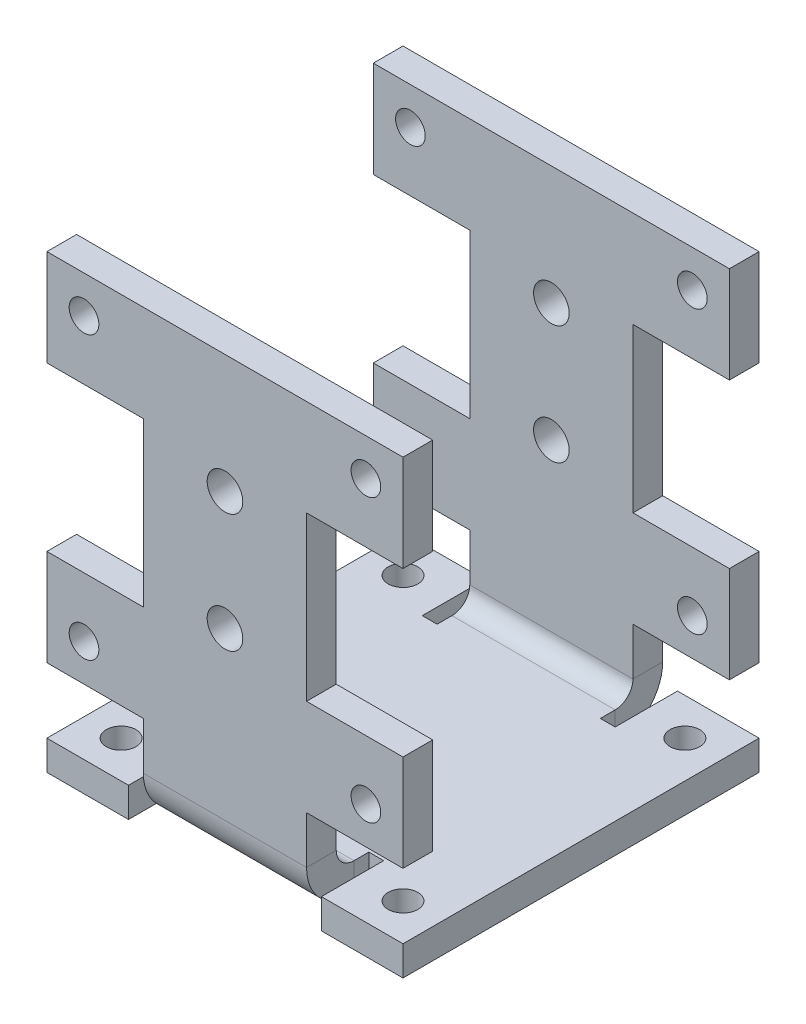
SolidWorks part; units mm, degrees
note: The reader was unsure of these and kept them because the rebuilt part matched: flange length of "边线-法兰1", "边线-法兰2".
material "5052-H36"
ref_plane "前视基准面" through (0, 0, 0) normal (0, 0, 1) x (1, 0, 0)
ref_plane "上视基准面" through (0, 0, 0) normal (0, 1, 0) x (1, 0, 0)
ref_plane "右视基准面" through (0, 0, 0) normal (1, 0, 0) x (0, 0, -1)
other "Configuration Table"
sketch "草图16" plane through (0, 0, 0) normal (0, 1, 0) x (1, 0, 0)
  line L0 (16.25, 30) -> (30, 30)
  line L5 (-30, -30) -> (-16.25, -30)
  line L6 (-30, -30) -> (-30, 30)
  line L11 (-30, 30) -> (-16.25, 30)
  line L12 (30, -30) -> (30, 30)
  line L17 (-30, -30) -> (30, 30) construction
  line L18 (-30, 30) -> (30, -30) construction
  line L19 (23.75, 23.75) -> (-23.75, 23.75) construction
  line L20 (23.75, 23.75) -> (23.75, -23.75) construction
  line L21 (23.75, -23.75) -> (-23.75, -23.75) construction
  line L22 (-23.75, 23.75) -> (-23.75, -23.75) construction
  line L23 (23.75, 23.75) -> (-23.75, -23.75) construction
  line L24 (23.75, -23.75) -> (-23.75, 23.75) construction
  line L26 (-16.25, 30) -> (-16.25, 23.75) construction
  line L27 (-16.25, 23.75) -> (16.25, 23.75) construction
  line L28 (16.25, 30) -> (16.25, 23.75) construction
  line L29 (-16.25, -23.75) -> (16.25, -23.75) construction
  line L30 (-16.25, -23.75) -> (-16.25, -30) construction
  line L32 (16.25, -23.75) -> (16.25, -30) construction
  line L33 (16.25, -30) -> (30, -30)
  line L34 (-16.25, -25) -> (-16.25, -30)
  line L35 (-16.25, -25) -> (16.25, -25)
  line L36 (-16.25, -25) -> (-16.25, 25) construction
  line L37 (-16.25, 25) -> (16.25, 25)
  line L38 (16.25, -25) -> (16.25, 25) construction
  line L39 (-16.25, -25) -> (16.25, 25) construction
  line L40 (-16.25, 25) -> (16.25, -25) construction
  line L41 (16.25, -25) -> (16.25, -30)
  line L42 (-16.25, 30) -> (-16.25, 25)
  line L43 (16.25, 30) -> (16.25, 25)
  circle A0 centre (-23.75, 23.75) radius 2.5
  circle A1 centre (-23.75, -23.75) radius 2.5
  circle A2 centre (-23.75, 23.75) radius 4.25 construction
  circle A3 centre (-23.75, -23.75) radius 4.25 construction
  circle A4 centre (23.75, 23.75) radius 2.5
  circle A5 centre (23.75, 23.75) radius 4.25 construction
  circle A6 centre (23.75, -23.75) radius 2.5
  circle A7 centre (23.75, -23.75) radius 4.25 construction
  point P0 (0, 0)
  point P6 (0, 0)
  point P23 (0, 0)
  point P24 (0, 23.75)
  point P29 (0, -23.75)
  dimension "D4" = 5
  dimension "D5" = 5
  dimension "D6" = 8.5
  dimension "D7" = 8.5
  dimension "D8" = 5
  dimension "D9" = 8.5
  dimension "D10" = 5
  dimension "D11" = 8.5
  dimension "D1" = 60
  dimension "D2" = 60
  dimension "D3" = 47.5
  dimension "D12" = 32.5
  dimension "D13" = 32.5
  dimension "D14" = 50
base flange "基体-法兰2" sketch "草图16" thickness 5 reverse thickness direction no parameters "D1"=0.7366
edge flange "边线-法兰1" sketch "草图19" flange angle 90 flange length 76 flange position material outside bend radius 3 thickness 5 relief rectangular parameters "D6"=10
sketch "草图19" plane through (0, 0, 25) normal (0, 0, 1) x (1, 0, 0)
  line L5 (-16.25, 0) -> (16.25, 0) construction
  line L6 (-13.75, 0) -> (13.75, 0)
  line L7 (-13.75, 0) -> (-13.75, 71)
  line L8 (-13.75, 71) -> (13.75, 71)
  line L9 (13.75, 0) -> (13.75, 71)
  point P6 (0, 0)
  dimension "D1" = 27.5
  dimension "D2" = 71
bend "边线折弯1" bend radius 3 bend angle 90 parameters "D5"=1
edge flange "边线-法兰2" sketch "草图22" flange angle 90 flange length 76 flange position material outside bend radius 3 thickness 5 relief rectangular parameters "D6"=10
sketch "草图22" plane through (0, 0, -25) normal (0, 0, -1) x (-1, 0, 0)
  line L6 (-13.75, 71) -> (13.75, 71)
  line L7 (-13.75, 71) -> (-13.75, 0)
  line L8 (-13.75, 0) -> (13.75, 0)
  line L9 (13.75, 71) -> (13.75, 0)
bend "边线折弯2" bend radius 3 bend angle 90 parameters "D5"=2
sketch "草图23" plane through (0, 0, 0) normal (0, 0, 1) x (1, 0, 0)
  line L0 (13.75, 71) -> (-13.75, 71) construction
  line L1 (-30, 71) -> (30, 71) construction
  line L2 (-30, 71) -> (-30, 11) construction
  line L3 (-30, 11) -> (30, 11) construction
  line L4 (30, 71) -> (30, 11) construction
  line L5 (-13.75, 71) -> (-13.75, 3) construction
  line L6 (-30, 71) -> (-13.75, 71)
  line L7 (-30, 71) -> (-30, 54.75)
  line L8 (-30, 54.75) -> (-13.75, 54.75)
  line L9 (-13.75, 71) -> (-13.75, 54.75)
  line L10 (13.75, 3) -> (13.75, 71) construction
  line L11 (13.75, 71) -> (30, 71)
  line L12 (13.75, 71) -> (13.75, 54.75)
  line L13 (13.75, 54.75) -> (30, 54.75)
  line L14 (30, 71) -> (30, 54.75)
  line L15 (30, 11) -> (13.75, 11)
  line L16 (30, 11) -> (30, 27.25)
  line L17 (30, 27.25) -> (13.75, 27.25)
  line L18 (13.75, 11) -> (13.75, 27.25)
  line L20 (-30, 11) -> (-13.75, 11)
  line L21 (-30, 11) -> (-30, 27.25)
  line L22 (-30, 27.25) -> (-13.75, 27.25)
  line L23 (-13.75, 11) -> (-13.75, 27.25)
  point P6 (0, 71)
  dimension "D1" = 60
  dimension "D2" = 60
  dimension "D3" = 16.25
  dimension "D4" = 16.25
extrude "凸台-拉伸1" add sketch "草图23" against normal up to surface (5 mm away) from surface at 30 up to face at (0, 37, 25) starting at face at (0, 37, 30)
sketch "草图24" plane through (0, 0, 0) normal (0, 0, 1) x (1, 0, 0)
  line L4 (30, 71) -> (13.75, 71)
  line L5 (30, 54.75) -> (30, 71)
  line L6 (13.75, 54.75) -> (30, 54.75)
  line L7 (13.75, 71) -> (13.75, 54.75)
  line L8 (30, 71) -> (13.75, 71)
  line L9 (30, 54.75) -> (30, 71)
  line L10 (13.75, 54.75) -> (30, 54.75)
  line L11 (13.75, 71) -> (13.75, 54.75)
  line L12 (-13.75, 71) -> (-30, 71)
  line L13 (-13.75, 54.75) -> (-13.75, 71)
  line L14 (-30, 54.75) -> (-13.75, 54.75)
  line L15 (-30, 71) -> (-30, 54.75)
  line L16 (-13.75, 71) -> (-30, 71)
  line L17 (-13.75, 54.75) -> (-13.75, 71)
  line L18 (-30, 54.75) -> (-13.75, 54.75)
  line L19 (-30, 71) -> (-30, 54.75)
  line L20 (-30, 11) -> (-13.75, 11)
  line L21 (-30, 27.25) -> (-30, 11)
  line L22 (-13.75, 27.25) -> (-30, 27.25)
  line L23 (-13.75, 11) -> (-13.75, 27.25)
  line L24 (-30, 11) -> (-13.75, 11)
  line L25 (-30, 27.25) -> (-30, 11)
  line L26 (-13.75, 27.25) -> (-30, 27.25)
  line L27 (-13.75, 11) -> (-13.75, 27.25)
  line L28 (13.75, 11) -> (30, 11)
  line L29 (30, 11) -> (30, 27.25)
  line L30 (30, 27.25) -> (13.75, 27.25)
  line L31 (13.75, 27.25) -> (13.75, 11)
  line L32 (13.75, 11) -> (30, 11)
  line L33 (30, 11) -> (30, 27.25)
  line L34 (30, 27.25) -> (13.75, 27.25)
  line L35 (13.75, 27.25) -> (13.75, 11)
  dimension "D1" = 0
  dimension "D2" = 0
  dimension "D3" = 0
  dimension "D4" = 0
extrude "凸台-拉伸2" add sketch "草图24" against normal up to surface (5 mm away) from surface at -25 up to face at (0, 37, -30) starting at face at (0, 37, -25)
sketch "草图25" plane through (0, 0, 0) normal (0, 0, 1) x (1, 0, 0)
  line L0 (-30, 71) -> (30, 11) construction
  line L1 (-30, 71) -> (30, 71) construction
  line L2 (-30, 71) -> (-30, 11) construction
  line L3 (-30, 11) -> (30, 11) construction
  line L4 (30, 71) -> (30, 11) construction
  line L5 (30, 71) -> (-30, 11) construction
  line L7 (-23.75, 17.25) -> (23.75, 17.25) construction
  line L8 (-23.75, 17.25) -> (-23.75, 64.75) construction
  line L9 (-23.75, 64.75) -> (23.75, 64.75) construction
  line L10 (23.75, 17.25) -> (23.75, 64.75) construction
  line L11 (-23.75, 17.25) -> (23.75, 64.75) construction
  line L12 (-23.75, 64.75) -> (23.75, 17.25) construction
  circle A0 centre (-23.75, 64.75) radius 2.5
  circle A1 centre (23.75, 64.75) radius 2.5
  circle A2 centre (-23.75, 17.25) radius 2.5
  circle A3 centre (23.75, 17.25) radius 2.5
  point P6 (0, 41)
  dimension "D2" = 5
  dimension "D3" = 5
  dimension "D4" = 5
  dimension "D5" = 5
  dimension "D1" = 47.5
extrude "切除-拉伸1" cut sketch "草图25" against normal through all and the other way through all normal cut yes
sketch "草图26" plane through (0, 0, 0) normal (0, 0, 1) x (1, 0, 0)
  line L0 (30, 71) -> (-30, 11) construction
  line L6 (-30, 71) -> (30, 11) construction
  line L8 (0, 31) -> (0, 51) construction
  circle A2 centre (0, 51) radius 3
  circle A3 centre (0, 31) radius 3
  point P8 (0, 41)
  dimension "D2" = 6
  dimension "D3" = 6
  dimension "D1" = 20
extrude "切除-拉伸2" cut sketch "草图26" against normal through all and the other way through all normal cut yes
sketch "折弯-线3" plane through (0, 0, 0) normal (0, 1, 0) x (1, 0, 0)
sketch "边界框3" plane through (0, 0, 0) normal (0, 1, 0) x (1, 0, 0)
sheet metal parameters "钣金10" thickness 5 parameters "D1"=0.7366
flat pattern "平板型式10" [suppressed]
sketch "折弯-线4" plane through (0, 0, 0) normal (0, 1, 0) x (1, 0, 0)
sketch "边界框4" [suppressed] plane through (0, 0, 0) normal (0, 1, 0) x (1, 0, 0)
sheet metal parameters "钣金21" thickness 5 parameters "D1"=0.7366
flat pattern "平板型式10" [suppressed]
sketch "折弯-线4" plane through (0, 0, 0) normal (0, 1, 0) x (1, 0, 0)
sketch "边界框4" [suppressed] plane through (0, 0, 0) normal (0, 1, 0) x (1, 0, 0)
bend of the flat pattern "展平-<边线折弯1>1"
sheet metal parameters "钣金22" thickness 5 parameters "D1"=0.7366
flat pattern "平板型式10" [suppressed]
sketch "折弯-线4" plane through (0, 0, 0) normal (0, 1, 0) x (1, 0, 0)
sketch "边界框4" [suppressed] plane through (0, 0, 0) normal (0, 1, 0) x (1, 0, 0)
bend of the flat pattern "展平-<边线折弯1>1"
bend of the flat pattern "展平-<边线折弯2>1"
sheet metal parameters "钣金23" thickness 5 parameters "D1"=0.7366
flat pattern "平板型式10" [suppressed]
sketch "折弯-线4" plane through (0, 0, 0) normal (0, 1, 0) x (1, 0, 0)
sketch "边界框4" [suppressed] plane through (0, 0, 0) normal (0, 1, 0) x (1, 0, 0)
bend of the flat pattern "展平-<边线折弯1>1"
bend of the flat pattern "展平-<边线折弯2>1"
sheet metal parameters "钣金24" thickness 5 parameters "D1"=0.7366
flat pattern "平板型式10" [suppressed]
sketch "折弯-线4" plane through (0, 0, 0) normal (0, 1, 0) x (1, 0, 0)
sketch "边界框4" [suppressed] plane through (0, 0, 0) normal (0, 1, 0) x (1, 0, 0)
bend of the flat pattern "展平-<边线折弯1>1"
bend of the flat pattern "展平-<边线折弯2>1"
sheet metal parameters "钣金25" thickness 5 parameters "D1"=0.7366
flat pattern "平板型式10" [suppressed]
sketch "折弯-线4" plane through (0, 0, 0) normal (0, 1, 0) x (1, 0, 0)
sketch "边界框4" [suppressed] plane through (0, 0, 0) normal (0, 1, 0) x (1, 0, 0)
bend of the flat pattern "展平-<边线折弯1>1"
bend of the flat pattern "展平-<边线折弯2>1"
sheet metal parameters "钣金26" thickness 5 parameters "D1"=0.7366
flat pattern "平板型式10" [suppressed]
sketch "折弯-线4" plane through (0, 0, 0) normal (0, 1, 0) x (1, 0, 0)
sketch "边界框4" [suppressed] plane through (0, 0, 0) normal (0, 1, 0) x (1, 0, 0)
bend of the flat pattern "展平-<边线折弯1>1"
bend of the flat pattern "展平-<边线折弯2>1"
